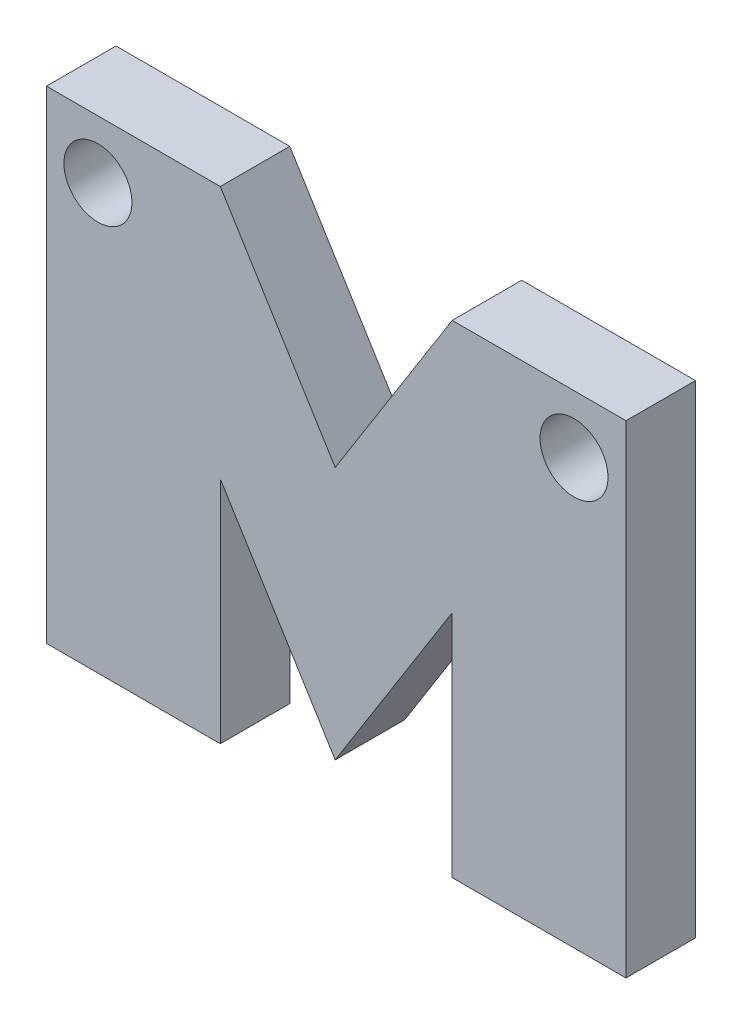
SolidWorks part; units mm, degrees
ref_plane "Front Plane" through (0, 0, 0) normal (0, 0, 1) x (1, 0, 0)
ref_plane "Top Plane" through (0, 0, 0) normal (0, 1, 0) x (1, 0, 0)
ref_plane "Right Plane" through (0, 0, 0) normal (1, 0, 0) x (0, 0, -1)
sketch "Sketch2" plane through (0, 0, 0) normal (0, 0, 1) x (1, 0, 0)
  line L0 (-126.7681, 49.2385) -> (-126.7681, -38.9328)
  line L1 (-126.7681, 49.2385) -> (-95.0181, 49.2385)
  line L2 (-95.0181, 49.2385) -> (-74.0249, 15.2678)
  line L3 (-74.0249, 15.2678) -> (-52.65, 49.2385)
  line L4 (-52.65, 49.2385) -> (-20.9, 49.2385)
  line L5 (-20.9, -38.9328) -> (-20.9, 49.2385)
  line L6 (-20.9, 49.2385) -> (-21.2817, 48.4751)
  line L7 (-126.7681, -38.9328) -> (-95.0181, -38.9328)
  line L8 (-95.0181, 2.9842) -> (-95.0181, -38.9328)
  line L9 (-95.0181, -38.9328) -> (-95.0181, -39.6962)
  line L10 (-95.0181, 2.9842) -> (-74.0249, -30.9866)
  line L11 (-74.0249, -30.9866) -> (-52.65, 2.9842)
  line L12 (-52.65, 2.9842) -> (-52.65, -38.9328)
  line L13 (-52.65, -38.9328) -> (-20.9, -38.9328)
  dimension "D1" = 31.75
  dimension "D2" = 88.1713
  dimension "D3" = 88.1713
  dimension "D4" = 31.75
extrude "Boss-Extrude2" add sketch "Sketch2" along normal blind 12.7 contours L12 L13 L5 L4 L3 L2 L1 L0 L7 L8 L10 L11 region at (-73.834, 6.183, 0)
sketch "Sketch3" plane through (0, 0, 0) normal (0, 0, -1) x (-1, 0, 0)
  line L0 (20.9, -38.9328) -> (20.9, 49.2385) construction
  line L1 (126.7681, 49.2385) -> (126.7681, -38.9328) construction
  circle A0 centre (30.3937, 38.6284) radius 6.2102
  circle A1 centre (117.3701, 38.6284) radius 6.2102
  dimension "D1" = 9.4937
  dimension "D2" = 9.398
extrude "Cut-Extrude1" cut sketch "Sketch3" against normal blind 12.7
